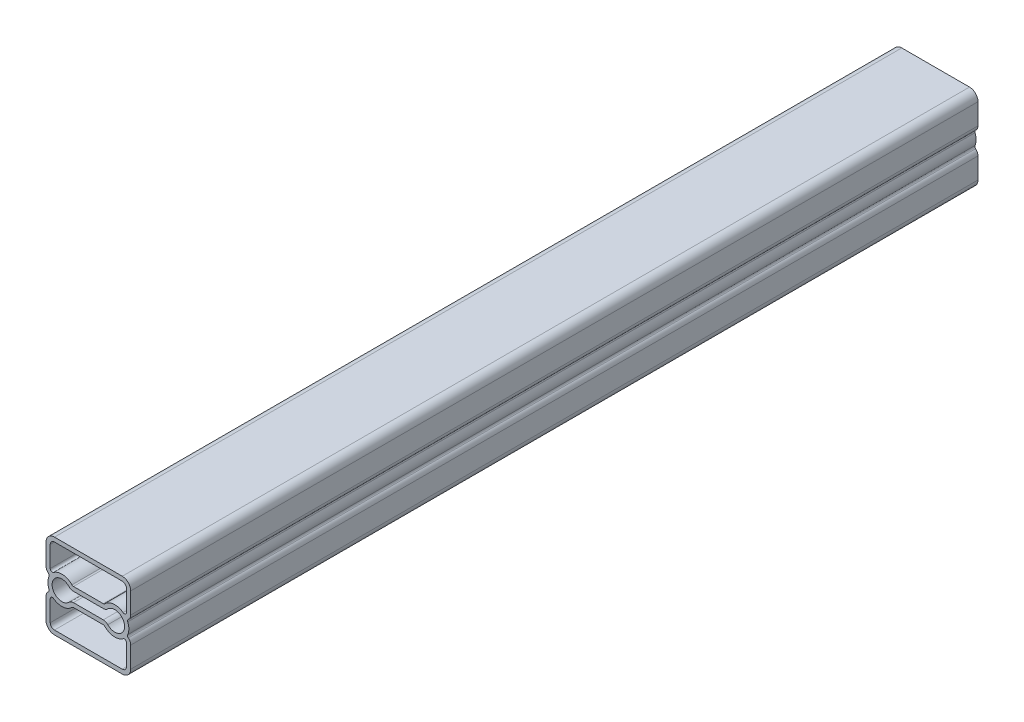
SolidWorks part; units mm, degrees
ref_plane "Front Plane" through (0, 0, 0) normal (0, 0, 1) x (1, 0, 0)
ref_plane "Top Plane" through (0, 0, 0) normal (0, 1, 0) x (1, 0, 0)
ref_plane "Right Plane" through (0, 0, 0) normal (1, 0, 0) x (0, 0, -1)
sketch "Sketch1" plane through (0, 0, 0) normal (0, 0, 1) x (1, 0, 0)
  line L0 (4.4671, -1.4668) -> (-4.4671, -1.4668)
  line L1 (-4.4671, 1.4668) -> (4.4671, 1.4668)
  line L2 (12.7, 3.9048) -> (12.7, 10.16)
  line L3 (10.16, 12.7) -> (-10.16, 12.7)
  line L4 (-12.7, 10.16) -> (-12.7, 3.9048)
  line L5 (-12.7, -3.9048) -> (-12.7, -10.16)
  line L6 (-10.16, -12.7) -> (10.16, -12.7)
  line L7 (12.7, -10.16) -> (12.7, -3.9048)
  line L8 (11.43, 10.16) -> (11.43, 3.9048)
  line L9 (4.4671, 2.7368) -> (-4.4671, 2.7368)
  line L10 (-11.43, 3.9048) -> (-11.43, 10.16)
  line L11 (-10.16, 11.43) -> (10.16, 11.43)
  line L12 (11.43, -3.9048) -> (11.43, -10.16)
  line L13 (10.16, -11.43) -> (-10.16, -11.43)
  line L14 (-11.43, -10.16) -> (-11.43, -3.9048)
  line L15 (-4.4671, -2.7368) -> (4.4671, -2.7368)
  arc A0 (5.8334, -2.0443) -> (4.4671, -1.4668) centre (4.4671, -3.3718) ccw
  arc A1 (-4.4671, -1.4668) -> (-5.8334, -2.0443) centre (-4.4671, -3.3718) ccw
  arc A2 (-5.8334, -2.0443) -> (-5.8334, 2.0443) centre (-7.9375, 0) cw
  arc A3 (-5.8334, 2.0443) -> (-4.4671, 1.4668) centre (-4.4671, 3.3718) ccw
  arc A4 (4.4671, 1.4668) -> (5.8334, 2.0443) centre (4.4671, 3.3718) ccw
  arc A5 (5.8334, 2.0443) -> (5.8334, -2.0443) centre (7.9375, 0) cw
  arc A6 (11.9832, 2.4158) -> (12.7, 3.9048) centre (10.795, 3.9048) ccw
  arc A7 (12.7, 10.16) -> (10.16, 12.7) centre (10.16, 10.16) ccw
  arc A8 (-10.16, 12.7) -> (-12.7, 10.16) centre (-10.16, 10.16) ccw
  arc A9 (-12.7, 3.9048) -> (-11.9832, 2.4158) centre (-10.795, 3.9048) ccw
  arc A10 (-11.9832, 2.4158) -> (-11.7963, 1.6675) centre (-12.3792, 1.9194) cw
  arc A11 (-11.7963, 1.6675) -> (-11.7963, -1.6675) centre (-7.9375, 0) ccw
  arc A12 (-11.7963, -1.6675) -> (-11.9832, -2.4158) centre (-12.3792, -1.9194) cw
  arc A13 (-11.9832, -2.4158) -> (-12.7, -3.9048) centre (-10.795, -3.9048) ccw
  arc A14 (-12.7, -10.16) -> (-10.16, -12.7) centre (-10.16, -10.16) ccw
  arc A15 (10.16, -12.7) -> (12.7, -10.16) centre (10.16, -10.16) ccw
  arc A16 (12.7, -3.9048) -> (11.9832, -2.4158) centre (10.795, -3.9048) ccw
  arc A17 (11.9832, -2.4158) -> (11.7963, -1.6675) centre (12.3792, -1.9194) cw
  arc A18 (11.7963, -1.6675) -> (11.7963, 1.6675) centre (7.9375, 0) ccw
  arc A19 (11.7963, 1.6675) -> (11.9832, 2.4158) centre (12.3792, 1.9194) cw
  arc A20 (10.16, 11.43) -> (11.43, 10.16) centre (10.16, 10.16) cw
  arc A21 (11.43, 3.9048) -> (10.42, 3.3924) centre (10.795, 3.9048) cw
  arc A22 (10.42, 3.3924) -> (4.9225, 2.9293) centre (7.9375, 0) ccw
  arc A23 (4.9225, 2.9293) -> (4.4671, 2.7368) centre (4.4671, 3.3718) cw
  arc A24 (-4.4671, 2.7368) -> (-4.9225, 2.9293) centre (-4.4671, 3.3718) cw
  arc A25 (-4.9225, 2.9293) -> (-10.42, 3.3924) centre (-7.9375, 0) ccw
  arc A26 (-10.42, 3.3924) -> (-11.43, 3.9048) centre (-10.795, 3.9048) cw
  arc A27 (-11.43, 10.16) -> (-10.16, 11.43) centre (-10.16, 10.16) cw
  arc A28 (4.4671, -2.7368) -> (4.9225, -2.9293) centre (4.4671, -3.3718) cw
  arc A29 (4.9225, -2.9293) -> (10.42, -3.3924) centre (7.9375, 0) ccw
  arc A30 (10.42, -3.3924) -> (11.43, -3.9048) centre (10.795, -3.9048) cw
  arc A31 (11.43, -10.16) -> (10.16, -11.43) centre (10.16, -10.16) cw
  arc A32 (-10.16, -11.43) -> (-11.43, -10.16) centre (-10.16, -10.16) cw
  arc A33 (-11.43, -3.9048) -> (-10.42, -3.3924) centre (-10.795, -3.9048) cw
  arc A34 (-10.42, -3.3924) -> (-4.9225, -2.9293) centre (-7.9375, 0) ccw
  arc A35 (-4.9225, -2.9293) -> (-4.4671, -2.7368) centre (-4.4671, -3.3718) cw
extrude "Boss-Extrude1" add sketch "Sketch1" against normal blind 254
